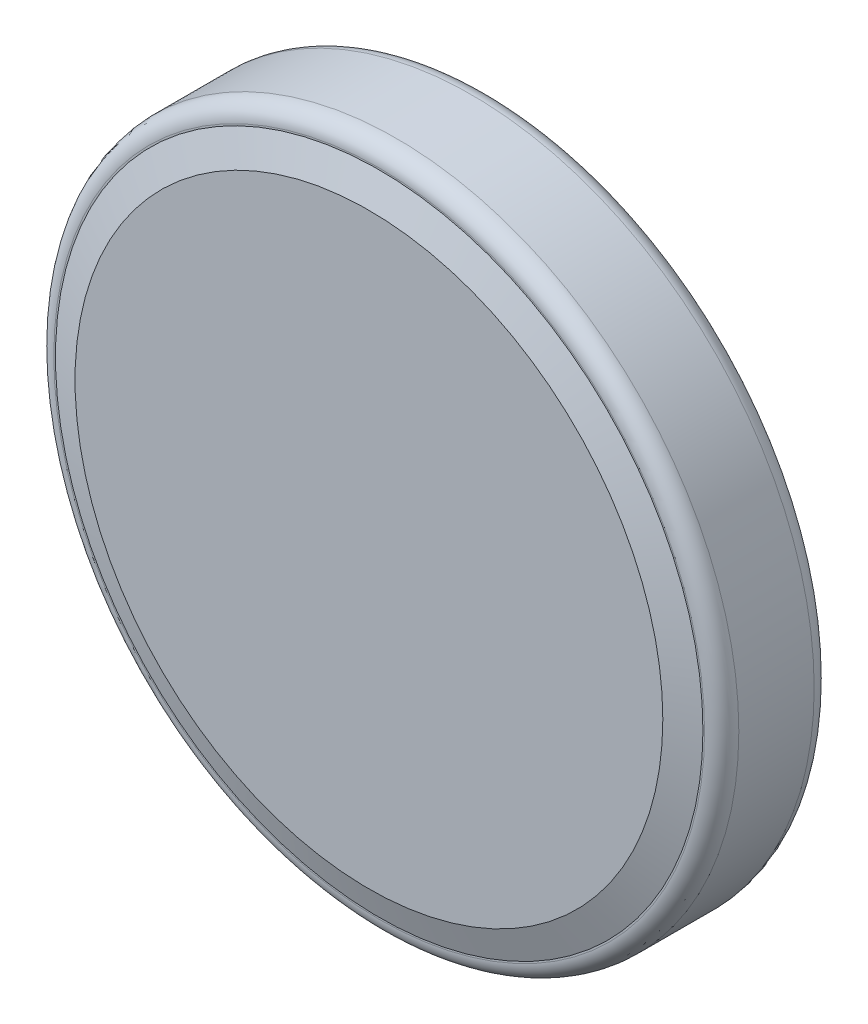
SolidWorks part; units mm, degrees
ref_plane "Alzado" through (0, 0, 0) normal (0, 0, 1) x (1, 0, 0)
ref_plane "Planta" through (0, 0, 0) normal (0, 1, 0) x (1, 0, 0)
ref_plane "Vista lateral" through (0, 0, 0) normal (1, 0, 0) x (0, 0, -1)
sketch "Sketch1" plane through (0, 0, 0) normal (0, 0, 1) x (1, 0, 0)
  circle A0 centre (0, 0) radius 10
  dimension "D1" = 20
extrude "Boss-Extrude1" add sketch "Sketch1" along normal blind 3.2
sketch "Sketch2" plane through (0, 0, 3.2) normal (0, 0, 1) x (1, 0, 0)
  circle A0 centre (0, 0) radius 8
  dimension "D1" = 16
extrude "Boss-Extrude2" add sketch "Sketch2" along normal blind 0.3
chamfer "Chamfer1" distance 0.5 angle 71 1 edges at (8, 0, 3.2) first distance on face at (8, 0, 3.5)
sketch "Sketch3" plane through (0, 0, 0) normal (0, 0, -1) x (-1, 0, 0)
  line L0 (0, 8.5) -> (0, 3.5) construction
  line L1 (-2.5, 6) -> (2.5, 6) construction
  line L2 (0.3, 8.5) -> (0.3, 3.5)
  line L3 (-2.5, 6.3) -> (2.5, 6.3)
  line L4 (-0.3, 8.5) -> (-0.3, 3.5)
  line L5 (-2.5, 5.7) -> (2.5, 5.7)
  line L6 (0.3, 8.5) -> (-0.3, 8.5)
  line L7 (0.3, 3.5) -> (-0.3, 3.5)
  line L8 (-2.5, 6.3) -> (-2.5, 5.7)
  line L9 (2.5, 6.3) -> (2.5, 5.7)
  line L10 (-9.2171, -2) -> (9.2171, -2) construction
  line L11 (-3.4571, -6.85) -> (4.5429, -6.85) construction
  text T0 "CR2450" font "Century Gothic" height 3.5
  text T1 "3V" font "Century Gothic" height 3.5
  point P5 (0, 6)
  point P6 (0, 6)
  point P17 (0, -2)
  point P21 (0.5429, -6.85)
  dimension "D1" = 5
  dimension "D2" = 5
  dimension "D3" = 0.3
  dimension "D5" = 6
  dimension "D6" = 2
  dimension "D7" = 8
  dimension "D4" = 0.3
extrude "Cut-Extrude1" cut sketch "Sketch3" against normal blind 0.1 contours L9 L3 L2 L5 | L2 L6 L4 L3 | L3 L8 L5 L4 | L4 L5 L2 L3 | L7 L2 L5 L4 region at (0, 7.4, 0) region at (-1.4, 6, 0) region at (0, 6, 0) region at (0, 4.6, 0) region at (1.4, 6, 0)
sketch "Sketch5" plane through (0, 0, 0) normal (0, 0, -1) x (-1, 0, 0)
  line L1 (-9.2171, -1.4607) -> (9.2171, -1.4607) construction
  line L2 (-4, -6.7761) -> (4, -6.7761) construction
  text T0 "CR2032" font "Century Gothic" height 3.5
  text T1 "3V" font "Century Gothic" height 3.5
  point P4 (0, -1.4607)
  point P7 (0, -6.7761)
  dimension "D1" = 8
extrude "Cut-Extrude2" cut sketch "Sketch5" against normal blind 0.1
fillet "Fillet1" radius 0.5 2 edges at (10, 0, 3.2) (10, 0, 0)
